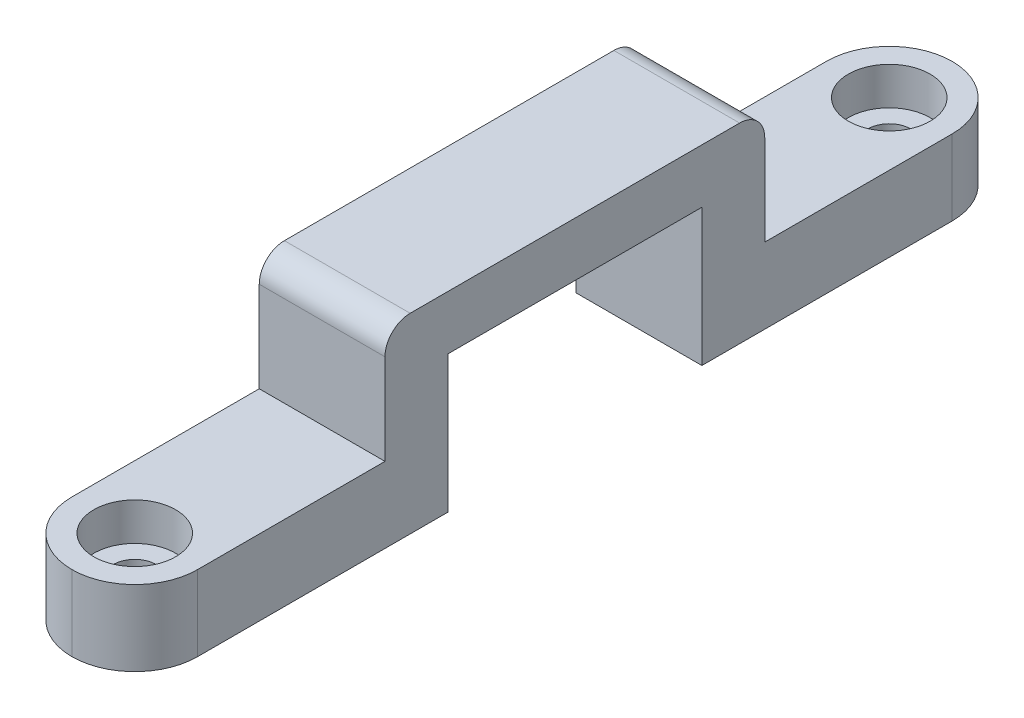
SolidWorks part; units mm, degrees
material "Filme de alta densidade PE"
ref_plane "Plano frontal" through (0, 0, 0) normal (0, 0, 1) x (1, 0, 0)
ref_plane "Plano superior" through (0, 0, 0) normal (0, 1, 0) x (1, 0, 0)
ref_plane "Plano direito" through (0, 0, 0) normal (1, 0, 0) x (0, 0, -1)
sketch "Esboço1" plane through (0, 0, 0) normal (1, 0, 0) x (0, 0, -1)
  line L0 (0, 0) -> (0, 6)
  line L1 (0, 6) -> (19.9, 6)
  line L2 (19.9, 6) -> (19.9, 15.2)
  line L3 (19.9, 15.2) -> (50.1, 15.2)
  line L4 (50.1, 15.2) -> (50.1, 6)
  line L5 (50.1, 6) -> (70, 6)
  line L6 (70, 6) -> (70, 0)
  line L7 (70, 0) -> (0, 0)
  point P10 (0, 0)
  dimension "D1" = 70
  dimension "D2" = 15.2
  dimension "D6" = 19.9
  dimension "D7" = 6
extrude "Ressalto-extrusão1" add sketch "Esboço1" along normal blind 10
hole_wizard "Rebaixo para SHCS M31" positions "Esboço2" profile "Esboço3" counterbore size "M3" standard "Ansi Metric" end condition through all
sketch "Esboço2" plane through (0, 6, 0) normal (0, 1, 0) x (1, 0, 0)
  line L3 (10, 0) -> (0, 0) construction
  line L6 (5, 70) -> (5, 65) construction
  line L7 (10, 70) -> (0, 70) construction
  line L9 (5, 5) -> (5, 0) construction
  point P0 (5, 5)
  point P26 (5, 65)
  dimension "D1" = 60
sketch "Esboço3" plane through (5, 6, -5) normal (1, 0, 0) x (0, 0, 1)
  line L0 (0, 0) -> (0, 6)
  line L1 (0, 6) -> (1.7, 6)
  line L3 (1.7, 6) -> (1.7, 3)
  line L4 (1.7, 3) -> (3.25, 3)
  line L5 (3.25, 3) -> (3.25, 0)
  line L7 (3.25, 0) -> (0, 0)
  line L11 (0, -6.35) -> (0, 107.95) construction
  dimension "Thru Hole Dia." = 3.4
  dimension "Thru Hole Depth" = 6
  dimension "C'Bore Dia." = 6.5
  dimension "C'Bore Depth" = 3
sketch "Esboço5" plane through (10, 0, 0) normal (1, 0, 0) x (0, 0, -1)
  line L0 (0, 0) -> (70, 0) construction
  line L1 (24.9, 0) -> (45.1, 0)
  line L2 (24.9, 0) -> (24.9, 10.9)
  line L3 (24.9, 10.9) -> (45.1, 10.9)
  line L4 (45.1, 0) -> (45.1, 10.9)
  line L8 (50.1, 15.2) -> (19.9, 15.2) construction
  point P6 (35, 10.9)
  point P9 (35, 15.2)
  dimension "D1" = 20.2
  dimension "D2" = 10.9
extrude "Corte-extrusão1" cut sketch "Esboço5" against normal through all
fillet "Filete1" radius 5 4 edges at (10, 3, 0) (0, 3, 0) (10, 3, -70) (0, 3, -70)
fillet "Filete2" radius 2 2 edges at (5, 15.2, -19.9) (5, 15.2, -50.1)
